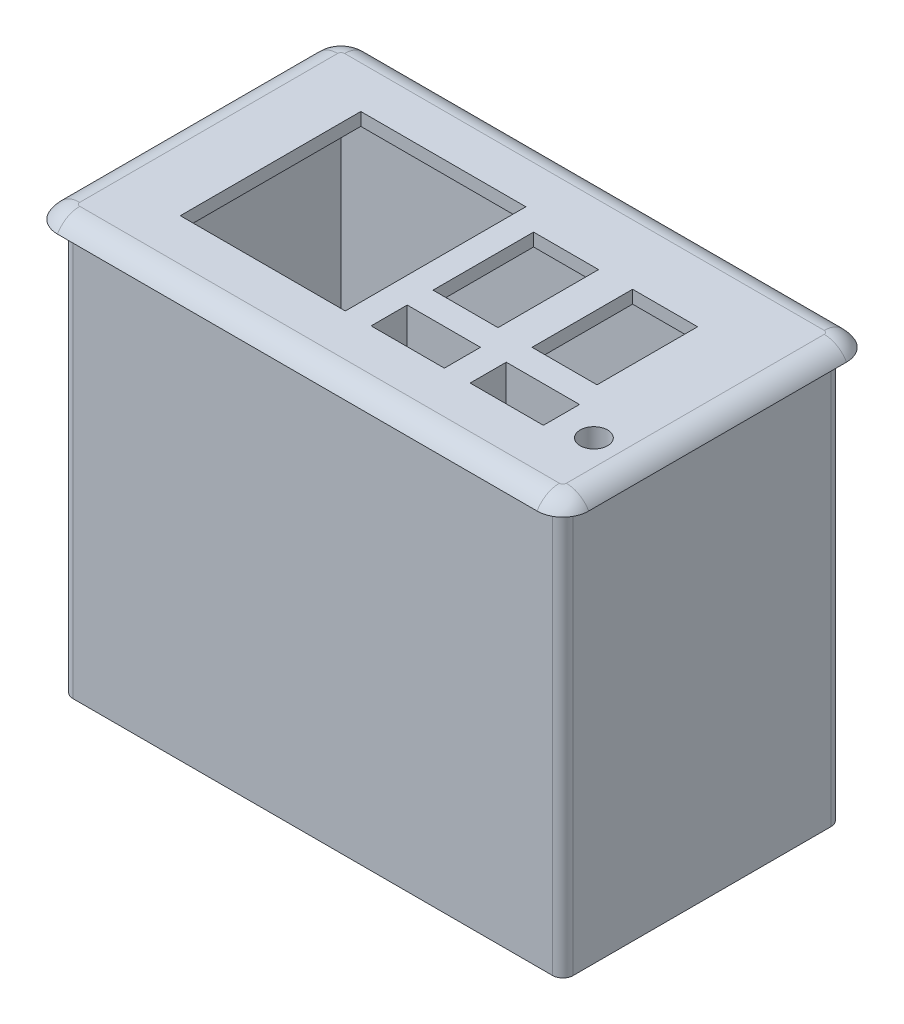
SolidWorks part; units mm, degrees
ref_plane "Front Plane" through (0, 0, 0) normal (0, 0, 1) x (1, 0, 0)
ref_plane "Top Plane" through (0, 0, 0) normal (0, 1, 0) x (1, 0, 0)
ref_plane "Right Plane" through (0, 0, 0) normal (1, 0, 0) x (0, 0, -1)
sketch "Sketch1" plane through (0, 0, 0) normal (0, 1, 0) x (1, 0, 0)
  line L1 (-46.5, 30) -> (46.5, 30)
  line L2 (-51.5, 25) -> (-51.5, -25)
  line L3 (-46.5, -30) -> (46.5, -30)
  line L4 (51.5, 25) -> (51.5, -25)
  line L5 (-51.5, 30) -> (51.5, -30) construction
  line L6 (-51.5, -30) -> (51.5, 30) construction
  arc A0 (46.5, -30) -> (51.5, -25) centre (46.5, -25) ccw
  arc A1 (51.5, 25) -> (46.5, 30) centre (46.5, 25) ccw
  arc A2 (-46.5, -30) -> (-51.5, -25) centre (-46.5, -25) cw
  arc A3 (-46.5, 30) -> (-51.5, 25) centre (-46.5, 25) ccw
  point P0 (0, 0)
  dimension "D3" = 5
  dimension "D1" = 103
  dimension "D2" = 60
extrude "Boss-Extrude1" add sketch "Sketch1" along normal blind 2.5
fillet "Fillet1" radius 5 8 edges at (-50.0355, 2.5, -28.5355) (0, 2.5, -30) (50.0355, 2.5, -28.5355) (51.5, 2.5, 0) (50.0355, 2.5, 28.5355) (0, 2.5, 30) (-50.0355, 2.5, 28.5355) (-51.5, 2.5, 0)
sketch "Sketch2" plane through (0, 0, 0) normal (0, -1, 0) x (1, 0, 0)
  line L0 (0, 30) -> (0, -30) construction
  line L5 (-46.5, 30) -> (46.5, 30) construction
  line L6 (46.5, -30) -> (-46.5, -30) construction
  line L7 (-51.5, 0) -> (51.5, 0) construction
  line L8 (-51.5, -25) -> (-51.5, 25) construction
  line L9 (51.5, 25) -> (51.5, -25) construction
  line L39 (-30.35, 28.5) -> (-30.35, -31.9661) construction
  line L40 (30.35, 28.5) -> (30.35, -35.5794) construction
  line L81 (46.5, 25) -> (-46.5, 25)
  line L82 (-46.5, 25) -> (-46.5, -25)
  line L83 (-46.5, -25) -> (46.5, -25)
  line L84 (46.5, -25) -> (46.5, 25)
  line L85 (48.5, -25) -> (48.5, 25)
  line L86 (-46.5, -27) -> (46.5, -27)
  line L87 (-48.5, 25) -> (-48.5, -25)
  line L88 (46.5, 27) -> (-46.5, 27)
  line L89 (48.5, -25) -> (48.5, 25)
  line L90 (-46.5, -27) -> (46.5, -27)
  line L91 (-48.5, 25) -> (-48.5, -25)
  line L92 (46.5, 27) -> (-46.5, 27)
  arc A16 (-46.5, 25) -> (-46.5, 25) centre (-46.5, 25) ccw
  arc A17 (-46.5, -25) -> (-46.5, -25) centre (-46.5, -25) ccw
  arc A18 (46.5, -25) -> (46.5, -25) centre (46.5, -25) ccw
  arc A19 (46.5, 25) -> (46.5, 25) centre (46.5, 25) ccw
  arc A20 (48.5, 25) -> (46.5, 27) centre (46.5, 25) ccw
  arc A21 (46.5, -27) -> (48.5, -25) centre (46.5, -25) ccw
  arc A22 (-48.5, -25) -> (-46.5, -27) centre (-46.5, -25) ccw
  arc A23 (-46.5, 27) -> (-48.5, 25) centre (-46.5, 25) ccw
  arc A24 (48.5, 25) -> (46.5, 27) centre (46.5, 25) ccw
  arc A25 (46.5, -27) -> (48.5, -25) centre (46.5, -25) ccw
  arc A26 (-48.5, -25) -> (-46.5, -27) centre (-46.5, -25) ccw
  arc A27 (-46.5, 27) -> (-48.5, 25) centre (-46.5, 25) ccw
  dimension "D3" = 2
  dimension "D5" = 2
  dimension "D1" = 3
  dimension "D2" = 2
  dimension "D4" = 93
  dimension "D6" = 97
extrude "Boss-Extrude2" add sketch "Sketch2" along normal blind 77
sketch "Sketch8" plane through (0, 0, 0) normal (0, -1, 0) x (1, 0, 0)
  line L0 (-51.5, 0) -> (51.5, 0) construction
  line L1 (-35.1815, 17.5) -> (-3.1815, 17.5)
  line L2 (-35.1815, 17.5) -> (-35.1815, -17.5)
  line L3 (-35.1815, -17.5) -> (-3.1815, -17.5)
  line L4 (-3.1815, 17.5) -> (-3.1815, -17.5)
  line L5 (-51.5, -25) -> (-51.5, 25) construction
  line L6 (51.5, 25) -> (51.5, -25) construction
  line L8 (1.8185, 17.5) -> (16.0185, 17.5)
  line L9 (1.8185, 17.5) -> (1.8185, 10.5)
  line L10 (1.8185, 10.5) -> (16.0185, 10.5)
  line L11 (16.0185, 17.5) -> (16.0185, 10.5)
  line L12 (21.0185, 17.5) -> (35.2185, 17.5)
  line L13 (21.0185, 17.5) -> (21.0185, 10.5)
  line L14 (21.0185, 10.5) -> (35.2185, 10.5)
  line L15 (35.2185, 17.5) -> (35.2185, 10.5)
  line L16 (1.8185, 5.5) -> (14.4185, 5.5)
  line L17 (1.8185, 5.5) -> (1.8185, -14)
  line L18 (1.8185, -14) -> (14.4185, -14)
  line L19 (14.4185, 5.5) -> (14.4185, -14)
  line L20 (21.0185, 5.5) -> (33.6185, 5.5)
  line L21 (21.0185, 5.5) -> (21.0185, -14)
  line L22 (21.0185, -14) -> (33.6185, -14)
  line L23 (33.6185, 5.5) -> (33.6185, -14)
  circle A0 centre (42.2185, 14.7069) radius 2.6601
  dimension "D10" = 5.3203
  dimension "D1" = 32
  dimension "D2" = 35
  dimension "D3" = 17.5
  dimension "D4" = 14.2
  dimension "D5" = 7
  dimension "D6" = 14.2
  dimension "D7" = 7
  dimension "D8" = 5
  dimension "D9" = 5
  dimension "D11" = 7
  dimension "D12" = 5
  dimension "D13" = 5
  dimension "D14" = 5
  dimension "D15" = 12.6
  dimension "D16" = 12.6
  dimension "D17" = 19.5
  dimension "D18" = 19.5
extrude "Cut-Extrude3" cut sketch "Sketch8" against normal blind 10
sketch "Sketch9" plane through (0, 0, 0) normal (0, -1, 0) x (1, 0, 0)
  line L0 (35.2185, 10.5) -> (35.2185, 17.5) construction
  line L1 (21.0185, 10.5) -> (35.2185, 10.5) construction
  line L2 (35.2185, 17.5) -> (21.0185, 17.5) construction
  line L3 (21.0185, 17.5) -> (21.0185, 10.5) construction
  line L4 (1.8185, 10.5) -> (16.0185, 10.5) construction
  line L5 (16.0185, 10.5) -> (16.0185, 17.5) construction
  line L6 (16.0185, 17.5) -> (1.8185, 17.5) construction
  line L7 (1.8185, 17.5) -> (1.8185, 10.5) construction
  line L8 (35.2185, 10.5) -> (35.2185, 17.5)
  line L9 (21.0185, 10.5) -> (35.2185, 10.5)
  line L10 (35.2185, 17.5) -> (21.0185, 17.5)
  line L11 (21.0185, 17.5) -> (21.0185, 10.5)
  line L12 (1.8185, 10.5) -> (16.0185, 10.5)
  line L13 (16.0185, 10.5) -> (16.0185, 17.5)
  line L14 (16.0185, 17.5) -> (1.8185, 17.5)
  line L15 (1.8185, 17.5) -> (1.8185, 10.5)
  line L16 (0.8185, 9.5) -> (17.0185, 9.5)
  line L17 (17.0185, 9.5) -> (17.0185, 18.5)
  line L18 (17.0185, 18.5) -> (0.8185, 18.5)
  line L19 (0.8185, 18.5) -> (0.8185, 9.5)
  line L20 (36.2185, 9.5) -> (36.2185, 18.5)
  line L21 (36.2185, 18.5) -> (20.0185, 18.5)
  line L22 (20.0185, 18.5) -> (20.0185, 9.5)
  line L23 (20.0185, 9.5) -> (36.2185, 9.5)
  circle A0 centre (42.2185, 14.7069) radius 2.6601 construction
  circle A1 centre (42.2185, 14.7069) radius 2.6601
  circle A2 centre (42.2185, 14.7069) radius 3.6601
  dimension "D1" = 1
  dimension "D2" = 1
  dimension "D3" = 1
extrude "Boss-Extrude4" add sketch "Sketch9" along normal blind 5
sketch "Sketch10" plane through (0, -77, 0) normal (0, -1, 0) x (1, 0, 0)
  line L0 (46.5, 25) -> (-46.5, 25) construction
  line L1 (46.5, 25) -> (41.5, 25)
  line L2 (-46.5, 25) -> (-46.5, -25) construction
  line L3 (-46.5, 25) -> (-46.5, 20)
  line L4 (-46.5, -25) -> (46.5, -25) construction
  line L5 (-46.5, -25) -> (-41.5, -25)
  line L6 (46.5, -25) -> (46.5, 25) construction
  line L7 (46.5, -25) -> (46.5, -20)
  line L8 (-46.5, 20) -> (-41.5, 20)
  line L9 (-41.5, 20) -> (-41.5, 25)
  line L10 (41.5, 25) -> (41.5, 20)
  line L11 (41.5, 20) -> (46.5, 20)
  line L12 (-46.5, 0) -> (46.5, 0) construction
  line L13 (41.5, -20) -> (46.5, -20)
  line L14 (41.5, -25) -> (41.5, -20)
  line L15 (-46.5, -20) -> (-41.5, -20)
  line L16 (-41.5, -20) -> (-41.5, -25)
  line L17 (46.5, 20) -> (46.5, 25)
  line L18 (-41.5, 25) -> (-46.5, 25)
  line L19 (-46.5, -20) -> (-46.5, -25)
  line L20 (41.5, -25) -> (46.5, -25)
  dimension "D1" = 5
  dimension "D2" = 5
  dimension "D3" = 5
  dimension "D4" = 5
extrude "Boss-Extrude5" add sketch "Sketch10" against normal blind 10
sketch "Sketch11" plane through (0, -77, 0) normal (0, -1, 0) x (1, 0, 0)
  line L0 (46.5, 27) -> (-46.5, 27) construction
  line L1 (46.5, 27) -> (-46.5, 27)
  line L2 (48.5, -25) -> (48.5, 25) construction
  line L3 (48.5, -25) -> (48.5, 25)
  line L4 (-46.5, -27) -> (46.5, -27) construction
  line L5 (-46.5, -27) -> (46.5, -27)
  line L6 (-48.5, 25) -> (-48.5, -25) construction
  line L7 (-48.5, 25) -> (-48.5, -25)
  line L8 (46.5, 25) -> (-46.5, 25)
  line L9 (-46.5, 25) -> (-46.5, -25)
  line L10 (-46.5, -25) -> (46.5, -25)
  line L11 (46.5, -25) -> (46.5, 25)
  arc A0 (48.5, 25) -> (46.5, 27) centre (46.5, 25) ccw construction
  arc A1 (48.5, 25) -> (46.5, 27) centre (46.5, 25) ccw
  arc A2 (46.5, -27) -> (48.5, -25) centre (46.5, -25) ccw construction
  arc A3 (46.5, -27) -> (48.5, -25) centre (46.5, -25) ccw
  arc A4 (-48.5, -25) -> (-46.5, -27) centre (-46.5, -25) ccw construction
  arc A5 (-48.5, -25) -> (-46.5, -27) centre (-46.5, -25) ccw
  arc A6 (-46.5, 27) -> (-48.5, 25) centre (-46.5, 25) ccw construction
  arc A7 (-46.5, 27) -> (-48.5, 25) centre (-46.5, 25) ccw
  arc A8 (-46.5, 25) -> (-46.5, 25) centre (-46.5, 25) ccw
  arc A9 (-46.5, -25) -> (-46.5, -25) centre (-46.5, -25) ccw
  arc A10 (46.5, -25) -> (46.5, -25) centre (46.5, -25) ccw
  arc A11 (46.5, 25) -> (46.5, 25) centre (46.5, 25) ccw
  dimension "D2" = 93
  dimension "D3" = 50
  dimension "D1" = 2
extrude "Boss-Extrude6" add sketch "Sketch11" along normal blind 2.5
sketch "Sketch12" plane through (0, -77, 0) normal (0, -1, 0) x (1, 0, 0)
  line L0 (-44, 25) -> (-44, 20) construction
  line L1 (-41.5, 25) -> (-46.5, 25) construction
  line L2 (-46.5, 20) -> (-41.5, 20) construction
  line L3 (-46.5, 22.5) -> (-41.5, 22.5) construction
  line L4 (-46.5, 25) -> (-46.5, 20) construction
  line L5 (-41.5, 20) -> (-41.5, 25) construction
  line L6 (0, 27) -> (0, -27) construction
  line L7 (46.5, 27) -> (-46.5, 27) construction
  line L8 (-46.5, -27) -> (46.5, -27) construction
  line L9 (-48.5, 0) -> (48.5, 0) construction
  line L10 (-48.5, 25) -> (-48.5, -25) construction
  line L11 (48.5, -25) -> (48.5, 25) construction
  circle A0 centre (-44, 22.5) radius 1.15
  circle A1 centre (44, 22.5) radius 1.15
  circle A2 centre (44, -22.5) radius 1.15
  circle A3 centre (-44, -22.5) radius 1.15
  dimension "D1" = 2.3
  dimension "D2" = 2.5
  dimension "D3" = 2.5
extrude "Cut-Extrude4" cut sketch "Sketch12" against normal up to next
